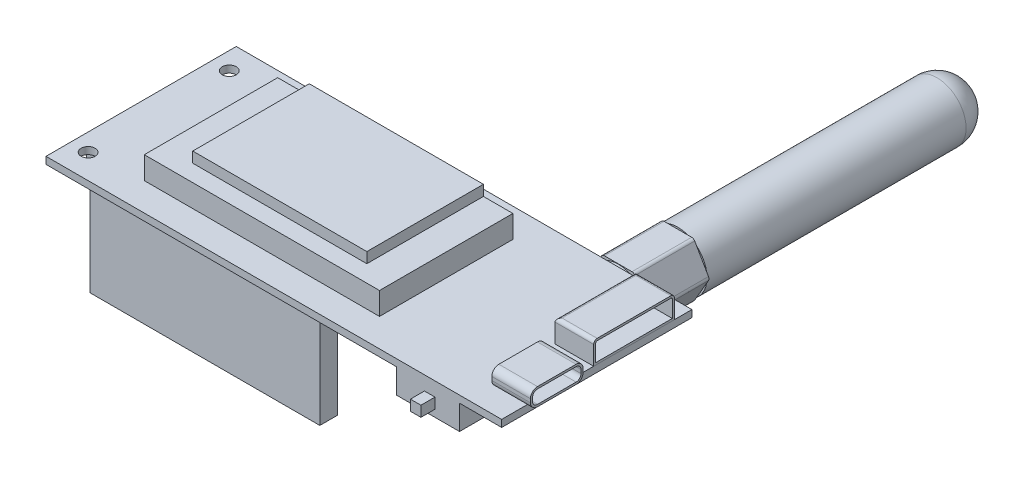
SolidWorks part; units mm, degrees
ref_plane "Alzado" through (0, 0, 0) normal (0, 0, 1) x (1, 0, 0)
ref_plane "Planta" through (0, 0, 0) normal (0, 1, 0) x (1, 0, 0)
ref_plane "Vista lateral" through (0, 0, 0) normal (1, 0, 0) x (0, 0, -1)
sketch "Croquis1" plane through (0, 0, 0) normal (0, 1, 0) x (1, 0, 0)
  line L0 (0, 0) -> (-32.45, 0) construction
  line L1 (-32.45, 13.55) -> (32.45, 13.55)
  line L2 (-32.45, 13.55) -> (-32.45, -13.55)
  line L3 (-32.45, -13.55) -> (32.45, -13.55)
  line L4 (32.45, 13.55) -> (32.45, -13.55)
  line L5 (-32.45, 13.55) -> (32.45, -13.55) construction
  line L6 (-32.45, -13.55) -> (32.45, 13.55) construction
  circle A0 centre (-29.95, 10.05) radius 1
  circle A1 centre (-29.95, -10.05) radius 1
  point P0 (0, 0)
  point P10 (-29.95, 11.05)
  point P11 (-30.95, 10.05)
  dimension "D3" = 2
  dimension "D1" = 27.1
  dimension "D2" = 64.9
  dimension "D4" = 1.5
  dimension "D5" = 2.5
extrude "Saliente-Extruir1" add sketch "Croquis1" along normal blind 1
sketch "Croquis2" plane through (0, 1, 0) normal (0, 1, 0) x (1, 0, 0)
  line L0 (-32.45, -13.55) -> (32.45, -13.55) construction
  line L1 (-22.45, 9.45) -> (11.05, 9.45)
  line L2 (-22.45, 9.45) -> (-22.45, -9.55)
  line L3 (-22.45, -9.55) -> (11.05, -9.55)
  line L4 (11.05, 9.45) -> (11.05, -9.55)
  line L5 (-32.45, 13.55) -> (-32.45, -13.55) construction
  line L6 (32.45, -13.55) -> (32.45, 13.55) construction
  line L7 (32.45, 11.05) -> (26.95, 11.05)
  line L8 (32.45, 11.05) -> (32.45, -0.45)
  line L9 (32.45, -0.45) -> (26.95, -0.45)
  line L10 (26.95, 11.05) -> (26.95, -0.45)
  line L11 (32.45, 13.55) -> (-32.45, 13.55) construction
  dimension "D1" = 33.5
  dimension "D2" = 19
  dimension "D3" = 4
  dimension "D4" = 10
  dimension "D5" = 5.5
  dimension "D6" = 2.5
  dimension "D7" = 11.5
extrude "Saliente-Extruir2" add sketch "Croquis2" along normal blind 3.2 separate body
sketch "Croquis3" plane through (0, 4.2, 0) normal (0, 1, 0) x (1, 0, 0)
  line L0 (11.05, 9.45) -> (-22.45, 9.45) construction
  line L1 (-17.95, 9.45) -> (6.85, 9.45)
  line L2 (-17.95, 9.45) -> (-17.95, -7.15)
  line L3 (-17.95, -7.15) -> (6.85, -7.15)
  line L4 (6.85, 9.45) -> (6.85, -7.15)
  line L5 (-22.45, 9.45) -> (-22.45, -9.55) construction
  dimension "D1" = 24.8
  dimension "D2" = 16.6
  dimension "D3" = 4.5
extrude "Saliente-Extruir3" add sketch "Croquis3" along normal blind 1.5
sketch "Croquis4" plane through (0, 1, 0) normal (0, 1, 0) x (1, 0, 0)
  line L1 (27.95, -2.95) -> (33.45, -2.95)
  line L2 (27.95, -2.95) -> (27.95, -10.45)
  line L3 (27.95, -10.45) -> (33.45, -10.45)
  line L4 (33.45, -2.95) -> (33.45, -10.45)
  line L5 (32.45, -13.55) -> (32.45, 13.55) construction
  line L6 (26.95, -0.45) -> (32.45, -0.45) construction
  dimension "D1" = 5.5
  dimension "D2" = 7.5
  dimension "D3" = 2.5
  dimension "D4" = 1
extrude "Saliente-Extruir4" add sketch "Croquis4" along normal blind 2.5 separate body
fillet "Redondeo2" radius 1 4 edges at (30.7, 3.5, 2.95) (30.7, 3.5, 10.45) (30.7, 1, 2.95) (30.7, 1, 10.45)
shell "Vaciado1" thickness 0.3 removed face at (33.45, 2.25, 6.7)
fillet "Redondeo3" radius 0.5 3 edges at (26.95, 4.2, -5.3) (29.7, 4.2, -11.05) (29.7, 4.2, 0.45)
shell "Vaciado2" thickness 0.3 removed face at (32.45, 3.0012, -5.3)
sketch "Croquis5" plane through (0, 0, 0) normal (0, -1, 0) x (1, 0, 0)
  line L0 (-32.45, 13.55) -> (32.45, 13.55) construction
  line L1 (22.95, 4.45) -> (28.45, 4.45)
  line L2 (22.95, 4.45) -> (22.95, -3.05)
  line L3 (22.95, -3.05) -> (28.45, -3.05)
  line L4 (28.45, 4.45) -> (28.45, -3.05)
  line L5 (17.45, 13.55) -> (26.45, 13.55)
  line L6 (17.45, 13.55) -> (17.45, 10.05)
  line L7 (17.45, 10.05) -> (26.45, 10.05)
  line L8 (26.45, 13.55) -> (26.45, 10.05)
  line L9 (-32.45, -13.55) -> (-32.45, 13.55) construction
  line L10 (-32.45, 7.75) -> (-26.95, 7.75)
  line L11 (-32.45, 7.75) -> (-32.45, -6.05)
  line L12 (-32.45, -6.05) -> (-26.95, -6.05)
  line L13 (-26.95, 7.75) -> (-26.95, -6.05)
  line L14 (32.45, -13.55) -> (-32.45, -13.55) construction
  line L15 (32.45, 13.55) -> (32.45, -13.55) construction
  line L17 (-12.05, 9.05) -> (3.95, 9.05)
  line L18 (-12.05, 9.05) -> (-12.05, -5.45)
  line L19 (-12.05, -5.45) -> (3.95, -5.45)
  line L20 (3.95, 9.05) -> (3.95, -5.45)
  point P20 (0, -13.55)
  dimension "D1" = 5.5
  dimension "D2" = 13.8
  dimension "D3" = 7.5
  dimension "D4" = 9
  dimension "D5" = 3.5
  dimension "D6" = 6
  dimension "D7" = 5.5
  dimension "D8" = 7.5
  dimension "D9" = 10.5
  dimension "D10" = 4
  dimension "D11" = 16
  dimension "D12" = 14.5
  dimension "D13" = 4.5
  dimension "D14" = 28.5
extrude "Saliente-Extruir5" add sketch "Croquis5" along normal blind 3.5
sketch "Croquis6" plane through (0, 0, 13.55) normal (0, 0, 1) x (1, 0, 0)
  line L0 (26.45, -3.5) -> (26.45, 0) construction
  line L1 (21.45, -1) -> (22.95, -1)
  line L2 (21.45, -1) -> (21.45, -2.5)
  line L3 (21.45, -2.5) -> (22.95, -2.5)
  line L4 (22.95, -1) -> (22.95, -2.5)
  point P4 (26.45, -1.75)
  point P8 (22.95, -1.75)
  dimension "D1" = 1.5
  dimension "D2" = 3.5
extrude "Saliente-Extruir6" add sketch "Croquis6" along normal blind 2
fillet "Redondeo4" radius 1 2 edges at (-26.95, -3.5, 0.85) (-32.45, -3.5, 0.85)
fillet "Redondeo5" radius 0.5 8 edges at (3.95, -1.75, 9.05) (3.95, -1.75, -5.45) (3.95, -3.5, 1.8) (-4.05, -3.5, -5.45) (-12.05, -1.75, -5.45) (-12.05, -1.75, 9.05) (-12.05, -3.5, 1.8) (-4.05, -3.5, 9.05)
sketch "Croquis7" plane through (0, 0, 0) normal (0, -1, 0) x (1, 0, 0)
  line L0 (32.45, 13.55) -> (32.45, -13.55) construction
  line L1 (14.95, -5.05) -> (20.95, -5.05)
  line L2 (14.95, -5.05) -> (14.95, -11.05)
  line L3 (14.95, -11.05) -> (20.95, -11.05)
  line L4 (20.95, -5.05) -> (20.95, -11.05)
  line L5 (32.45, -13.55) -> (-32.45, -13.55) construction
  dimension "D1" = 6
  dimension "D2" = 11.5
  dimension "D3" = 2.5
extrude "Saliente-Extruir7" add sketch "Croquis7" along normal blind 9.5
fillet "Redondeo6" radius 0.5 4 edges at (20.95, -4.75, -11.05) (14.95, -4.75, -11.05) (14.95, -4.75, -5.05) (20.95, -4.75, -5.05)
fillet "Redondeo7" radius 1 8 edges at (15.0964, -9.5, -10.9036) (14.95, -9.5, -8.05) (15.0964, -9.5, -5.1964) (17.95, -9.5, -5.05) (20.8036, -9.5, -5.1964) (20.95, -9.5, -8.05) (20.8036, -9.5, -10.9036) (17.95, -9.5, -11.05)
sketch "Croquis8" plane through (0, 0, -11.05) normal (0, 0, -1) x (-1, 0, 0)
  line L0 (-20.45, -8.5) -> (-15.45, -8.5) construction
  line L1 (-15.95, -9.5) -> (-19.95, -9.5) construction
  circle A0 centre (-17.95, -6.5) radius 2.5
  point P2 (-17.95, -8.5)
  point P7 (-17.95, -9)
  dimension "D2" = 5
  dimension "D1" = 0.5
extrude "Saliente-Extruir9" add sketch "Croquis8" along normal blind 4 and the other way blind 1
sketch "Croquis9" plane through (0, 0, -15.05) normal (0, 0, -1) x (-1, 0, 0)
  circle A0 centre (-17.95, -6.5) radius 3.85
  dimension "D1" = 7.7
extrude "Saliente-Extruir10" add sketch "Croquis9" along normal blind 2.5
sketch "Croquis10" plane through (0, 0, -17.55) normal (0, 0, -1) x (-1, 0, 0)
  line L1 (-15.7, -10.3971) -> (-13.45, -6.5)
  line L2 (-13.45, -6.5) -> (-15.7, -2.6029)
  line L3 (-15.7, -2.6029) -> (-20.2, -2.6029)
  line L4 (-20.2, -2.6029) -> (-22.45, -6.5)
  line L5 (-22.45, -6.5) -> (-20.2, -10.3971)
  line L6 (-20.2, -10.3971) -> (-15.7, -10.3971)
  circle A0 centre (-17.95, -6.5) radius 3.8971 construction
  dimension "D1" = 4.5
extrude "Saliente-Extruir11" add sketch "Croquis10" along normal blind 8.5
fillet "Redondeo9" radius 0.5 6 edges at (20.2, -2.6029, -21.8) (15.7, -2.6029, -21.8) (13.45, -6.5, -21.8) (15.7, -10.3971, -21.8) (20.2, -10.3971, -21.8) (22.45, -6.5, -21.8)
sketch "Croquis11" plane through (0, 0, -26.05) normal (0, 0, -1) x (-1, 0, 0)
  line L0 (-15.9887, -2.6029) -> (-19.9113, -2.6029) construction
  circle A0 centre (-17.95, -6.5) radius 4.15
  arc A1 (-13.5943, -6.75) -> (-13.5943, -6.25) centre (-14.0274, -6.5) ccw construction
  point P2 (-13.5274, -6.5)
  point P3 (-17.95, -2.6029)
  dimension "D1" = 8.3
extrude "Saliente-Extruir12" add sketch "Croquis11" along normal blind 41
fillet "Redondeo10" radius 4.1 1 edges at (13.8, -6.5, -67.05)
sketch "Croquis12" plane through (0, 0, 0) normal (0, -1, 0) x (1, 0, 0)
  line L0 (0, 0) -> (32.45, 0) construction
  line L1 (32.45, 13.55) -> (32.45, -13.55) construction
  line L2 (-32.45, 13.55) -> (17.45, 13.55) construction
  line L3 (-26.95, 12.75) -> (5.75, 12.75)
  line L4 (-26.95, 12.75) -> (-26.95, 10.25)
  line L5 (-26.95, 10.25) -> (5.75, 10.25)
  line L6 (5.75, 12.75) -> (5.75, 10.25)
  line L7 (-32.45, -6.05) -> (-32.45, 7.75) construction
  line L8 (-26.95, -10.25) -> (5.75, -10.25)
  line L9 (5.75, -12.75) -> (5.75, -10.25)
  line L10 (-26.95, -12.75) -> (5.75, -12.75)
  line L11 (-26.95, -12.75) -> (-26.95, -10.25)
  point P17 (-26.95, 11.5)
  point P18 (-26.95, -11.5)
  dimension "D1" = 2.5
  dimension "D2" = 32.7
  dimension "D3" = 0.8
  dimension "D4" = 5.5
extrude "Saliente-Extruir13" add sketch "Croquis12" along normal blind 13.5
